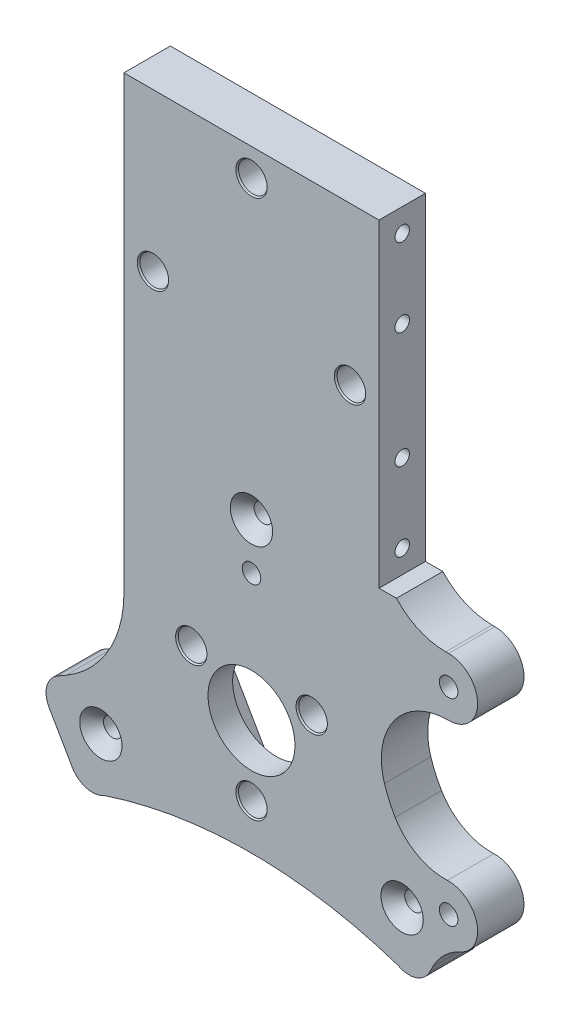
SolidWorks part; units mm, degrees
ref_plane "Front Plane" through (0, 0, 0) normal (0, 0, 1) x (1, 0, 0)
ref_plane "Top Plane" through (0, 0, 0) normal (0, 1, 0) x (1, 0, 0)
ref_plane "Right Plane" through (0, 0, 0) normal (1, 0, 0) x (0, 0, -1)
sketch "Sketch1" plane through (0, 0, 0) normal (0, 0, 1) x (1, 0, 0)
  line L0 (-1000, 0) -> (49000, 0) construction
  line L1 (0, -1000) -> (0, 49000) construction
  line L2 (0, 0) -> (-37.6779, -21.7533) construction
  line L3 (0, 0) -> (34.4865, -19.9108) construction
  line L4 (10, -8.7457) -> (10, 8.7457) construction
  line L5 (10.3863, 10.4956) -> (-10.3863, 10.4956)
  line L6 (-14.2847, 3.7444) -> (-3.9035, -14.2421)
  line L7 (3.9036, -14.242) -> (14.2846, 3.7447)
  line L8 (9.0941, -5.2486) -> (-10.3863, 5.9944) construction
  line L9 (0, -11.9891) -> (0, 10.4956) construction
  line L10 (10.3863, 5.9946) -> (-9.0941, -5.2488) construction
  line L11 (-30.909, -22.4641) -> (-34.909, -15.5359)
  line L12 (-32, -9.2376) -> (-33.4449, -10.0718)
  line L13 (-25, -23.6714) -> (-25.4449, -23.9282)
  line L14 (24.7944, -23.6821) -> (25.2453, -23.9282)
  line L15 (30.7512, -22.1827) -> (34.3345, -14.8973)
  line L16 (22, 49.7573) -> (-22, 49.7573)
  line L17 (22, 49.7573) -> (22, 38.5054)
  line L18 (32, -9.2376) -> (32.7451, -9.6678)
  line L19 (-22, 49.7573) -> (-22, 8.0829)
  line L20 (-4, 6.9282) -> (-41.6779, -14.8251) construction
  line L21 (34, 27.0109) -> (33.4945, 27.0109)
  line L22 (34, 17.0109) -> (33.8909, 17.0109)
  line L25 (-12, 0) -> (-12.0927, -0.0535)
  circle A0 centre (0, 0) radius 30 construction
  circle A1 centre (0, 0) radius 7.5
  circle A2 centre (0, 30) radius 4 construction
  circle A3 centre (25.9808, -15) radius 4 construction
  circle A4 centre (-25.9808, -15) radius 4 construction
  arc A5 (-10.3863, 10.4956) -> (-14.2847, 3.7444) centre (-10.3863, 5.9944) ccw
  arc A6 (-3.9035, -14.2421) -> (3.9036, -14.242) centre (0, -11.9891) ccw
  arc A7 (14.2846, 3.7447) -> (10.3863, 10.4956) centre (10.3863, 5.9946) ccw
  circle A8 centre (37.5, 42.204) radius 2.5
  circle A9 centre (-37.5, 42.204) radius 2.5
  arc A10 (32, -9.2376) -> (22.9322, 2.0481) centre (42, 8.0829) cw
  arc A11 (-22, 8.0829) -> (-32, -9.2376) centre (-42, 8.0829) cw
  arc A12 (25.2453, -23.9282) -> (-25.4449, -23.9282) centre (-0.0998, -99.8072) ccw
  arc A13 (30.7512, -22.1827) -> (25.2453, -23.9282) centre (27.1619, -20.4173) cw
  arc A14 (32.7451, -9.6678) -> (34.3345, -14.8973) centre (30.7451, -13.1319) cw
  arc A15 (-30.909, -22.4641) -> (-25.4449, -23.9282) centre (-27.4449, -20.4641) ccw
  arc A16 (-33.4449, -10.0718) -> (-34.909, -15.5359) centre (-31.4449, -13.5359) ccw
  circle A17 centre (34, -11.9891) radius 5
  arc A18 (34, 17.0109) -> (34, 27.0109) centre (34, 22.0109) ccw
  arc A19 (22, 38.5054) -> (33.4945, 27.0109) centre (33.4945, 38.5054) ccw
  arc A20 (33.8909, 17.0109) -> (22.9322, 2.0481) centre (33.8909, 5.5165) ccw
  point P4 (0, 0)
  point P19 (0, 0)
  point P21 (10, 0)
  point P40 (0, 0.9917)
  point P46 (0, 49.7573)
  point P47 (-32.909, -19)
  point P62 (28.909, -25.9282)
  point P67 (-28.909, -25.9282)
  line B0 (37, -11.9891) -> (-75, -11.9891) construction
  line B1 (0, -11.9891) -> (0, 22.0109) construction
  line B2 (-14.25, -36.1891) -> (-14.25, -11.9891) construction
  line B3 (-29.75, -13.311) -> (-29.75, -10.6672) construction
  line B4 (-39.75, -13.2558) -> (-39.75, -10.7223) construction
  line B5 (34, -11.9891) -> (34, 22.0109) construction
  line B6 (37, 27.0109) -> (37, -16.9891) construction
  line B7 (37, 27.0109) -> (-3, 27.0109) construction
  line B8 (37, -16.9891) -> (-3, -16.9891) construction
  line B9 (-14.25, -11.9891) -> (-14.25, 75.8256) construction
  line B10 (-3, 27.0109) -> (-3, -16.9891) construction
  dimension "D1" = 60
  dimension "D4" = 15
  dimension "D5" = 3
  dimension "D7" = 75
  dimension "D9" = 8
  dimension "D11" = 20
  dimension "D12" = 11.4945
  dimension "D13" = 4
  dimension "D14" = 4
  dimension "D15" = 11.4945
  dimension "D2" = 120
  dimension "D3" = 120
  dimension "D6" = 10
  dimension "D8" = 44
  dimension "D10" = 8
  dimension "D16" = 37.5
sketch_block_instance "HemeraFrontContraints-3"
sketch_block "HemeraFrontContraints" parameters "D1"=34, "D2"=48.25, "D3"=63.75, "D4"=73.75, "D5"=24.2, "D6"=34, "D7"=34, "D8"=31.699, "D9"=36.9763, "D10"=44
sketch "Sketch2" plane through (0, 0, 0) normal (0, 1, 0) x (1, 0, 0)
  line L0 (52, -10) -> (52, -104) construction
  line L1 (-49, 0) -> (49, 0) construction
  line L2 (-52, -10) -> (-52, -104) construction
  line L3 (-52, -104) -> (52, -104) construction
  line L4 (0, 0) -> (0, -30) construction
  line L7 (-52, -10) -> (-49, -10) construction
  line L8 (-49, 0) -> (-49, -10) construction
  line L11 (52, -10) -> (49, -10) construction
  line L12 (49, 0) -> (49, -10) construction
  point P12 (0, -104)
  dimension "D1" = 98
  dimension "D2" = 104
  dimension "D3" = 30
  dimension "D4" = 10
  dimension "D7" = 104
extrude "Boss-Extrude1" add sketch "Sketch1" along normal blind 8 contours A7 L7 A6 L6 A5 L5 | L17 | L19 | L16 L19 L17 | A10 A17 L15 A14 L18 | L15 A17 A10 L18 A14 region at (1.5486, 13.9173, 0) region at (31.8342, -12.7141, 0) region at (35.6729, -11.4291, 0)
extrude "Boss-Extrude2" add sketch "Sketch1<3>" along normal blind 4.25 from offset 3.75 contours L7 A7 L5 A5 L6 A6 A1 region at (13.936, 8.0445, 0)
sketch "Sketch1<3>" plane through (0, 0, 0) normal (0, 0, 1) x (1, 0, 0) same geometry as "Sketch1"
sketch "Sketch15" plane through (0, 49.7573, 0) normal (0, 1, 0) x (1, 0, 0)
  line L4 (22, 0) -> (-22, 0)
  line L5 (-22, 0) -> (-22, -8)
  line L6 (-22, -8) -> (22, -8)
  line L7 (22, -8) -> (22, 0)
  line L8 (22, 0) -> (-22, 0)
  line L9 (-22, 0) -> (-22, -8)
  line L10 (-22, -8) -> (22, -8)
  line L11 (22, -8) -> (22, 0)
  dimension "D1" = 0
extrude "Boss-Extrude3" add sketch "Sketch15" along normal blind 36
sketch "Sketch4" plane through (0, 0, 0) normal (0, 0, -1) x (-1, 0, 0)
  line L0 (0, 26) -> (0, 34)
  arc A0 (0, 26) -> (0, 34) centre (0, 30) ccw
revolve "Cut-Revolve1" cut sketch "Sketch4" angle 360 about L0
sketch "Sketch22" plane through (0, 0, 8) normal (0, 0, 1) x (1, 0, 0)
  line L0 (22, 49.7573) -> (22, 38.5054) construction
  line L1 (22, 40.7573) -> (27, 40.7573)
  line L2 (22, 40.7573) -> (22, 30.7573)
  line L3 (22, 30.7573) -> (27, 30.7573)
  line L4 (27, 40.7573) -> (27, 30.7573)
  dimension "D1" = 10
  dimension "D2" = 5
  dimension "D3" = 30.7573
extrude "Cut-Extrude1" cut sketch "Sketch22" against normal blind 10
sketch "Sketch5" plane through (0, 0, 0) normal (0, 0, -1) x (-1, 0, 0)
  line L0 (-22.5167, -13) -> (-29.4449, -17)
  line L1 (0, 0) -> (-34.4865, -19.9108) construction
  arc A0 (-22.5167, -13) -> (-29.4449, -17) centre (-25.9808, -15) ccw
revolve "Cut-Revolve2" cut sketch "Sketch5" angle 360 about L0
sketch "Sketch6" plane through (0, 0, 0) normal (0, 0, -1) x (-1, 0, 0)
  line L0 (22.5167, -13) -> (29.4449, -17)
  line L1 (0, 0) -> (37.6779, -21.7533) construction
  arc A0 (22.5167, -13) -> (29.4449, -17) centre (25.9808, -15) ccw
revolve "Cut-Revolve3" cut sketch "Sketch6" angle 360 about L0
hole_wizard "CSK for M3 Flat Head Machine Screw1" positions "Sketch7" profile "Sketch8" countersink size "M3" standard "ANSI Metric" end condition through all
sketch "Sketch7" plane through (0, 0, 8) normal (0, 0, 1) x (1, 0, 0)
  point P0 (0, 30)
  point P3 (25.9808, -15)
  point P6 (-25.9808, -15)
sketch "Sketch8" plane through (0, 30, 8) normal (1, 0, 0) x (0, -1, 0)
  line L0 (0, 0) -> (0, 8)
  line L1 (0, 8) -> (1.6, 8)
  line L2 (1.6, 8) -> (1.6, 2.05)
  line L3 (1.6, 2.05) -> (3.65, 0)
  line L5 (3.65, 0) -> (0, 0)
  line L6 (-1.6, 2.05) -> (-3.65, 0) construction
  line L11 (0, -6.35) -> (0, 107.95) construction
  dimension "Thru Hole Dia." = 3.2
  dimension "Thru Hole Depth" = 8
  dimension "Near C'Sink Dia." = 7.3
  dimension "Near C'Sink Angle" = 90
hole_wizard "CBORE for M3 SBHCS2" positions "Sketch11" profile "Sketch12" counterbore size "M3" standard "ANSI Metric" end condition through all
sketch "Sketch11" plane through (0, 0, 0) normal (0, 0, -1) x (-1, 0, 0)
  point P0 (-34, 22.0109)
  point P3 (0, 22.0109)
  point P6 (0, -11.9891)
  point P19 (-34, -11.9891)
sketch "Sketch12" plane through (34, 22.0109, 0) normal (1, 0, 0) x (0, 1, 0)
  line L0 (0, 0) -> (0, 8)
  line L1 (0, 8) -> (1.6, 8)
  line L3 (1.6, 8) -> (1.6, 3)
  line L4 (3.35, 3) -> (1.6, 3)
  line L5 (3.35, 3) -> (3.35, 0.025)
  line L6 (3.35, 0.025) -> (3.375, 0)
  line L7 (3.375, 0) -> (0, 0)
  line L8 (-3.35, 0.025) -> (-3.375, 0) construction
  line L11 (0, -6.35) -> (0, 107.95) construction
  dimension "Thru Hole Dia." = 3.2
  dimension "Thru Hole Depth" = 8
  dimension "C'Bore Dia." = 6.7
  dimension "C'Bore Depth" = 3
  dimension "Near C'Sink Dia." = 6.75
  dimension "Near C'Sink Angle" = 90
hole_wizard "CSK for M4 Flat Head Machine Screw1" positions "Sketch13" profile "Sketch14" countersink size "M4" standard "ANSI Metric" end condition through all
sketch "Sketch13" plane through (0, 0, 8) normal (0, 0, 1) x (1, 0, 0)
  point P0 (-10.3863, 5.9944)
  point P3 (10.3863, 5.9946)
  point P6 (0, -11.9891)
sketch "Sketch14" plane through (-10.3863, 5.9944, 8) normal (1, 0, 0) x (0, -1, 0)
  line L0 (0, 0) -> (0, 8)
  line L1 (0, 8) -> (2.5, 8)
  line L2 (2.5, 8) -> (2.5, 0.2606)
  line L3 (2.5, 0.2606) -> (2.7, 0)
  line L5 (2.7, 0) -> (0, 0)
  line L6 (-2.5, 0.2606) -> (-2.7, 0) construction
  line L11 (0, -6.35) -> (0, 107.95) construction
  dimension "Thru Hole Dia." = 5
  dimension "Thru Hole Depth" = 8
  dimension "Near C'Sink Dia." = 5.4
  dimension "Near C'Sink Angle" = 75
fillet "Fillet1" radius 10 2 edges at (30.5834, -8.3385, 4) (33.328, -16.9437, 4)
hole_wizard "Tap Drill for M3x0.5 Tap4" positions "Sketch25" profile "Sketch26" hole size "M3x0.5" standard "ANSI Metric"
sketch "Sketch25" plane through (22, 0, 0) normal (1, 0, 0) x (0, 0, -1)
  line L0 (-8, 85.7573) -> (0, 85.7573) construction
  line L1 (0, 85.7573) -> (0, 30.7573) construction
  point P0 (-4, 81.7573)
  point P2 (-4, 68.2573)
  point P4 (-4, 34.7573)
  point P6 (-4, 48.2573)
  dimension "D1" = 4
  dimension "D2" = 13.5
  dimension "D3" = 13.5
  dimension "D4" = 20
  dimension "D5" = 4
sketch "Sketch26" plane through (22, 81.7573, 4) normal (0, 1, 0) x (0, 0, -1)
  line L0 (0, 0) -> (0, 10.7511)
  line L1 (0, 10.7511) -> (1.25, 10)
  line L2 (1.25, 10) -> (1.25, 0)
  line L5 (1.25, 0) -> (0, 0)
  line L10 (0, 10.7511) -> (-1.25, 10) construction
  line L11 (0, -6.35) -> (0, 107.95) construction
  dimension "Hole Dia." = 2.5
  dimension "Hole Depth" = 10
  dimension "Drill Angle" = 118
mirror "Mirror1" about plane through (0, 0, 0) normal (1, 0, 0) of "Tap Drill for M3x0.5 Tap4"
sketch "Sketch27" plane through (0, 0, 0) normal (0, 0, -1) x (-1, 0, 0)
  line L0 (-22, 68.2799) -> (22, 68.2799) construction
  line L1 (-22, 85.7573) -> (-22, 30.7573) construction
  line L2 (22, 85.7573) -> (22, 8.0829) construction
  text T0 "HEMERA" font "Century Gothic" height 7.5
extrude "Cut-Extrude2" cut sketch "Sketch27" against normal blind 1
hole_wizard "CSK for M4 Flat Head Machine Screw2" positions "Sketch28" profile "Sketch29" countersink size "M4" standard "ANSI Metric" end condition through all
sketch "Sketch28" plane through (0, 0, 8) normal (0, 0, 1) x (1, 0, 0)
  line L0 (22, 85.7573) -> (22, 30.7573) construction
  point P0 (17, 58.6053)
  point P2 (-17, 58.6053)
  point P8 (0, 81.0063)
  dimension "D1" = 34
  dimension "D2" = 5
sketch "Sketch29" plane through (17, 58.6053, 8) normal (1, 0, 0) x (0, -1, 0)
  line L0 (0, 0) -> (0, 8)
  line L1 (0, 8) -> (2.5, 8)
  line L2 (2.5, 8) -> (2.5, 0.2606)
  line L3 (2.5, 0.2606) -> (2.7, 0)
  line L5 (2.7, 0) -> (0, 0)
  line L6 (-2.5, 0.2606) -> (-2.7, 0) construction
  line L11 (0, -6.35) -> (0, 107.95) construction
  dimension "Thru Hole Dia." = 5
  dimension "Thru Hole Depth" = 8
  dimension "Near C'Sink Dia." = 5.4
  dimension "Near C'Sink Angle" = 75
